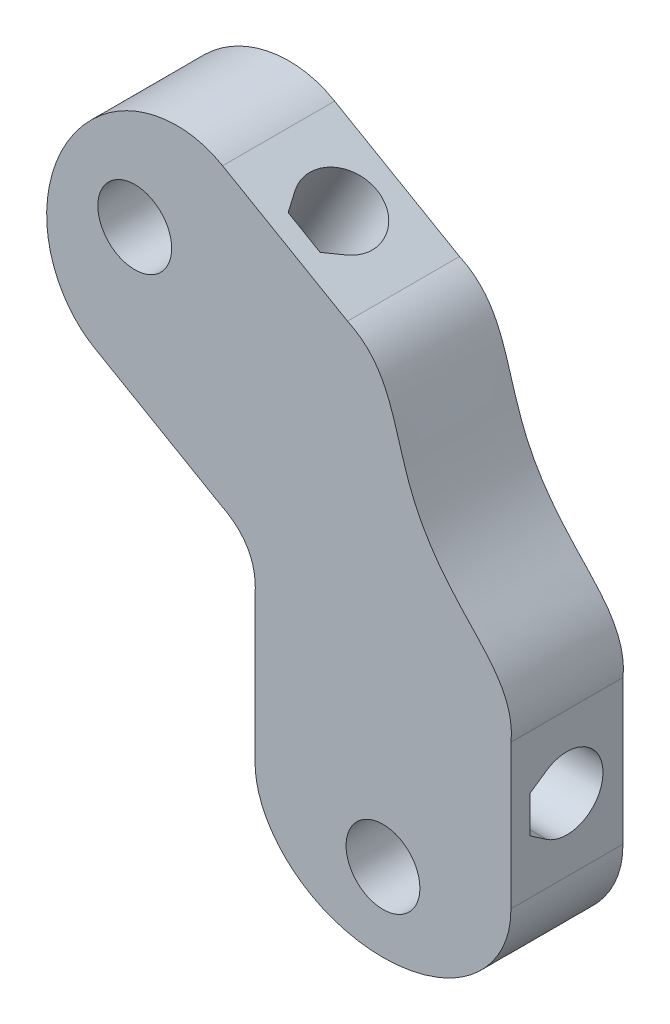
SolidWorks part; units mm, degrees
ref_plane "Piano frontale" through (0, 0, 0) normal (0, 0, 1) x (1, 0, 0)
ref_plane "Piano superiore" through (0, 0, 0) normal (0, 1, 0) x (1, 0, 0)
ref_plane "Piano destro" through (0, 0, 0) normal (1, 0, 0) x (0, 0, -1)
sketch "Model" plane through (0, 0, 0) normal (0, 0, 1) x (1, 0, 0)
  line L0 (-32.3853, 85.015) -> (-17.6641, 76.516)
  line L1 (-47.4753, 58.8776) -> (-32.7542, 50.3785)
  line L2 (-28.5624, 43.1722) -> (-28.5624, 26.1722)
  line L3 (1.5876, 43.1722) -> (1.5876, 26.1722)
  line L4 (-15.8086, 58.4351) -> (-23.9493, 53.7351)
  line L5 (-23.9493, 53.7351) -> (-22.6493, 51.4834)
  line L6 (-22.6493, 51.4834) -> (-29.3258, 52.2475)
  line L7 (-29.3258, 52.2475) -> (-26.5993, 58.325)
  line L8 (-26.5993, 58.325) -> (-25.2993, 56.0734)
  line L9 (-25.2993, 56.0734) -> (-17.1586, 60.7734)
  line L10 (-17.1586, 60.7734) -> (-15.8086, 58.4351)
  line L11 (-18.3993, 44.1222) -> (-25.0758, 44.8863)
  line L12 (-25.0758, 44.8863) -> (-22.3493, 50.9638)
  line L13 (-22.3493, 50.9638) -> (-21.0493, 48.7121)
  line L14 (-21.0493, 48.7121) -> (-12.9086, 53.4122)
  line L15 (-12.9086, 53.4122) -> (-11.5086, 50.9873)
  line L16 (-11.5086, 50.9873) -> (-19.6493, 46.2873)
  line L17 (-19.6493, 46.2873) -> (-18.3993, 44.1222)
  line L18 (-7.6874, 50.7686) -> (-10.0256, 49.4186)
  line L19 (-10.0256, 49.4186) -> (-17.8756, 63.0152)
  line L20 (-17.8756, 63.0152) -> (-15.5374, 64.3652)
  line L21 (-15.5374, 64.3652) -> (-7.6874, 50.7686)
  line L22 (-17.6641, 76.516) -> (-32.7542, 50.3785) construction
  line L23 (-32.3853, 85.015) -> (-47.4753, 58.8776) construction
  line L24 (1.5876, 43.1722) -> (-28.5624, 43.1722) construction
  line L25 (-28.5624, 26.1722) -> (1.5876, 26.1722) construction
  circle A0 centre (-13.4874, 22.9222) radius 4.35
  circle A1 centre (-42.7374, 73.5847) radius 4.35
  spline S0 degree 3 poles (-32.3853, 85.015) (-35.6002, 86.9166) (-41.4741, 86.6983) (-47.5594, 82.6446) (-50.9722, 78.3607) (-52.985, 73.2684) (-53.4773, 65.9555) (-50.7008, 60.7553) (-47.4753, 58.8776) knots 0 0 0 0 0.24929 0.374356 0.499525 0.624695 0.749762 1 1 1 1
  spline S1 degree 3 poles (-17.6641, 76.516) (-13.8887, 74.7963) (-12.1809, 69.346) (-10.1387, 62.3226) (-7.342, 57.3703) (-2.3112, 51.7096) (2.0516, 47.5864) (1.5876, 43.1722) knots 0 0 0 0 0.279426 0.419812 0.560238 0.707311 1 1 1 1
  spline S2 degree 3 poles (1.5876, 26.1722) (1.6269, 22.4337) (-1.5043, 17.4528) (-8.0658, 14.2116) (-13.4874, 13.4024) (-18.9089, 14.2116) (-25.4704, 17.4528) (-28.6017, 22.4338) (-28.5624, 26.1722) knots 0 0 0 0 0.249526 0.374712 0.5 0.625288 0.750474 1 1 1 1
  spline S3 degree 2 poles (-32.7542, 50.3785) (-28.1857, 48.161) (-28.5624, 43.1722) knots 0 0 0 1 1 1
extrude "Main body" add sketch "Model" along normal blind 13.2 contours L1 S3 L2 S2 L3 S1 L0 S0 | A0 | A1
extrude "Side up graphic" cut sketch "Model<4>" along normal blind 1 contours L10 L9 L8 L7 L6 L5 L4 | L14 L15 L16 L17 L11 L12 L13 | L19 L20 L21 L18 region at (-23.1283, 55.7767, 0)
sketch "Model<4>" plane through (0, 0, 0) normal (0, 0, 1) x (1, 0, 0) same geometry as "Model"
sketch "Schizzo5" plane through (1.5876, 0, 0) normal (1, 0, 0) x (0, 0, -1)
  line L0 (-13.2, 34.6722) -> (0, 34.6722) construction
  line L1 (-13.2, 43.1722) -> (-13.2, 26.1722) construction
  line L2 (0, 43.1722) -> (0, 26.1722) construction
  line L3 (-10.95, 32.4972) -> (-10.95, 36.8472)
  line L4 (-10.95, 32.4972) -> (-8.9978, 31.1632)
  line L5 (-10.95, 36.8472) -> (-8.9978, 38.1812)
  arc A0 (-8.9978, 31.1632) -> (-8.9978, 38.1812) centre (-6.6, 34.6722) ccw
  point P11 (-10.95, 34.6722)
  dimension "D2" = 8.5
  dimension "D1" = 2.25
  dimension "D3" = 4.35
extrude "Hole 1" cut sketch "Schizzo5" against normal up to next
sketch "Schizzo4" plane through (28.7161, 49.7391, 0) normal (0.5, 0.866, 0) x (0.866, -0.5, 0)
  line L0 (-62.0541, 0) -> (-62.0541, -13.2) construction
  line L1 (-70.5533, 0) -> (-53.5549, 0) construction
  line L2 (-70.5533, -13.2) -> (-53.5549, -13.2) construction
  line L3 (-64.2291, -10.95) -> (-59.8791, -10.95)
  line L4 (-64.2291, -10.95) -> (-65.5631, -8.9978)
  line L5 (-59.8791, -10.95) -> (-58.5451, -8.9978)
  arc A0 (-58.5451, -8.9978) -> (-65.5631, -8.9978) centre (-62.0541, -6.6) ccw
  point P11 (-62.0541, -10.95)
  dimension "D1" = 8.5
  dimension "D2" = 2.25
  dimension "D3" = 4.35
extrude "Hole 2" cut sketch "Schizzo4" against normal up to next contours A0 L4 L3 L5
ref_axis "Screwhole 1" through (-42.7374, 73.5847, 13.2) along (0, 0, -1)
ref_axis "Screwhole 2" through (-13.4874, 22.9222, 13.2) along (0, 0, -1)
ref_axis "Screwhole 3" through (-28.5624, 34.6722, 6.6) along (1, 0, 0)
ref_axis "Screwhole 4" through (-41.955, 51.4406, 6.6) along (0.5, 0.866, 0)
